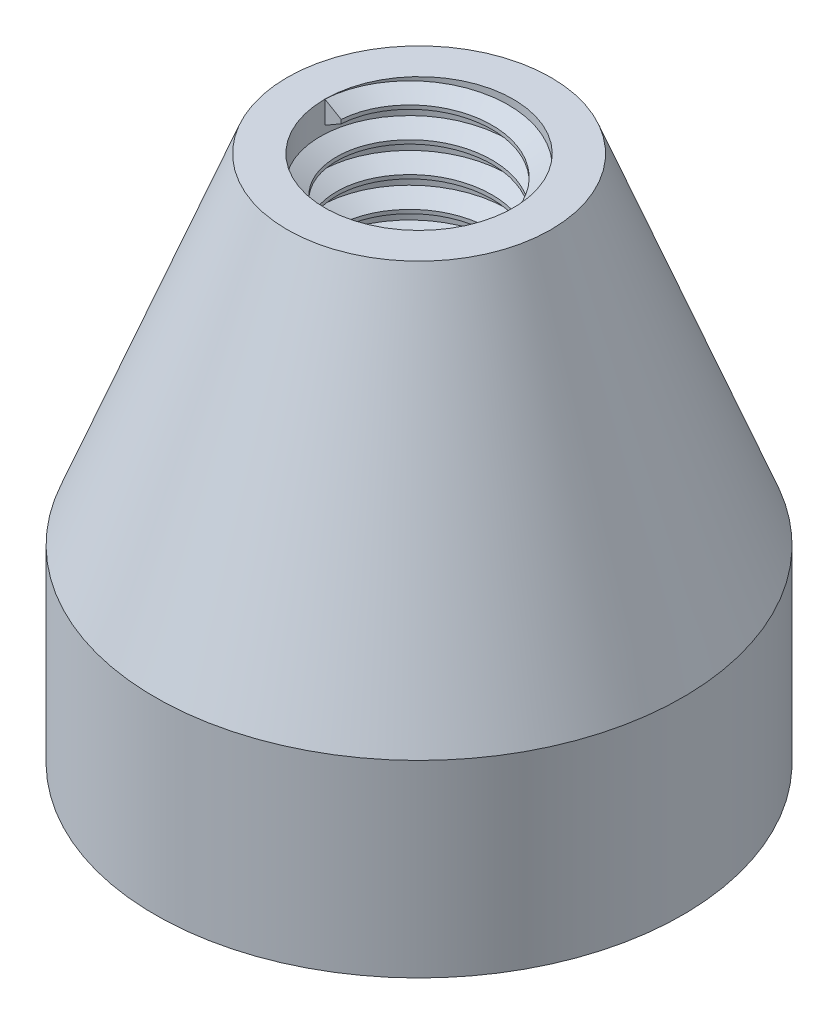
SolidWorks part; units mm, degrees
material "Commercial Bronze, UNS C22000 (90-10 Bronze)"
ref_plane "Front Plane" through (0, 0, 0) normal (0, 0, 1) x (1, 0, 0)
ref_plane "Top Plane" through (0, 0, 0) normal (0, 1, 0) x (1, 0, 0)
ref_plane "Right Plane" through (0, 0, 0) normal (1, 0, 0) x (0, 0, -1)
sketch "Sketch1" plane through (0, 0, 0) normal (1, 0, 0) x (0, 0, -1)
  line L0 (1780.0363, 1554.9799) -> (1778.0363, 1554.9799)
  line L1 (1773.0363, 1554.9799) -> (1773.0363, 1568.9799)
  line L2 (1775.5363, 1565.4874) -> (1775.5363, 1568.9799)
  line L3 (1780.0363, 1554.9799) -> (1780.0363, 1559.9799)
  line L4 (1776.5363, 1568.9799) -> (1775.5363, 1568.9799)
  line L5 (1780.0363, 1559.9799) -> (1776.5363, 1568.9799)
  line L6 (1778.0363, 1559.9799) -> (1775.5363, 1565.4874)
  line L7 (1778.0363, 1559.9799) -> (1778.0363, 1554.9799)
revolve "Revolve1" add sketch "Sketch1" angle 360 about L1 region at (0, 1561.7782, -1777.9725)
thread "Thread1" pitch 0.8 method extrude profile "Thread Profile1" start angle 0, offset 0, length 3.5, pitch 0.8, diameter 5
ref_plane "Plane2" through (-2.5, 1568.9799, -1773.0363) normal (0, 0, 1) x (-1, 0, 0)
sketch "Thread Profile1" plane through (-2.5, 1568.9799, -1773.0363) normal (0, 0, 1) x (-1, 0, 0)
  line L0 (0, 0) -> (0, 0.8) construction
  line L1 (0, 0.6) -> (-0.433, 0.35)
  line L2 (-0.433, 0.35) -> (-0.433, 0.25)
  line L3 (-0.433, 0.25) -> (0, 0)
  line L4 (-0.433, 0.3) -> (0, 0.3) construction
  line L11 (0, 0.6) -> (0, 0)
  point P6 (0, 0)
  dimension "Pitch" = 0.8
  dimension "Profile_Angle" = 60
  dimension "Profile_Land" = 0.1
  dimension "Profile_Height" = 0.433
